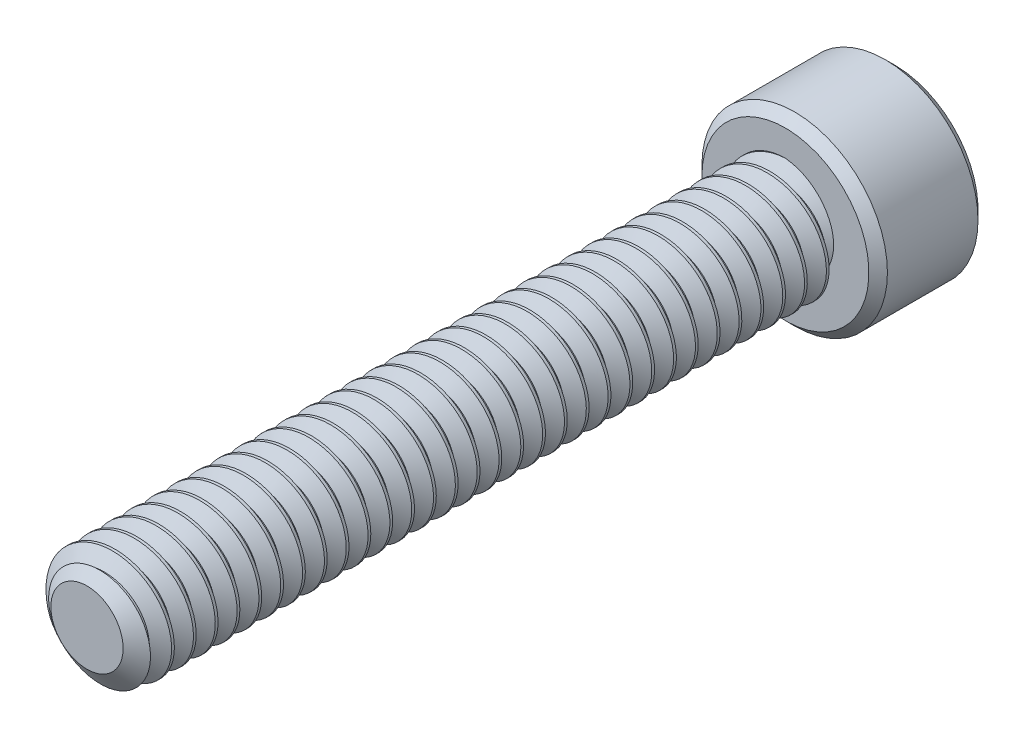
SolidWorks part; units mm, degrees
other "DetailItem1"
ref_plane "Front Plane" through (0, 0, 0) normal (0, 0, 1) x (1, 0, 0)
ref_plane "Top Plane" through (0, 0, 0) normal (0, 1, 0) x (1, 0, 0)
ref_plane "Right Plane" through (0, 0, 0) normal (1, 0, 0) x (0, 0, -1)
sketch "Sketch1" plane through (0, 0, 0) normal (0, 0, 1) x (1, 0, 0)
  circle A0 centre (0, 0) radius 2.0828
  dimension "OD" = 4.1656
extrude "Extrude1" add sketch "Sketch1" against normal blind 25.4
sketch "Sketch2" plane through (0, 0, 0) normal (0, 0, 1) x (1, 0, 0)
  circle A0 centre (0, 0) radius 2.0828 construction
  circle A1 centre (0, 0) radius 2.0828
curve "Helix/Spiral1" pitch 0.7937 height 26.1937 turns 33 parameters "pitch"=0.7937
sketch "Sketch3" plane through (0, 0, 0) normal (1, 0, 0) x (0, 0, -1)
  line L0 (-0.6945, 2.0828) -> (-0.3969, 1.5672)
  line L1 (-0.3969, 1.5672) -> (-0.2977, 1.5672)
  line L2 (-0.2977, 1.5672) -> (0, 2.0828)
  line L3 (-0.6945, 2.0828) -> (0, 2.0828)
  line L4 (-0.3473, 2.0828) -> (-0.3473, 1.5672) construction
  line L5 (-0.5457, 1.825) -> (-0.1488, 1.825) construction
  line L6 (0, 2.0828) -> (0, -2.0828) construction
  dimension "D1" = 0.0992
  dimension "D2" = 0.3969
  dimension "D3" = 60
sweep "Cut-Sweep1" cut profiles "Sketch3" path "Helix/Spiral1"
sketch "Sketch4" plane through (0, 0, 0) normal (1, 0, 0) x (0, 0, -1)
  line L0 (0.5388, 2.0828) -> (0, 1.3132)
  line L1 (0, 1.3132) -> (0, 2.0828)
  line L2 (0.5388, 2.0828) -> (0, 2.0828)
  line L3 (-0.6945, 2.0828) -> (0, 2.0828) construction
  line L4 (0, 0) -> (7.0209, 0) construction
  dimension "D1" = 55
  dimension "D2" = 0.254
revolve "Cut-Revolve1" cut sketch "Sketch4" angle 360 about L4
sketch "Sketch6" plane through (0, 0, -25.4) normal (0, 0, -1) x (-1, 0, 0)
  circle A0 centre (0, 0) radius 3.3734
  dimension "head dia" = 6.7469
extrude "Extrude2" add sketch "Sketch6" along normal blind 3.9688
sketch "Sketch7" plane through (0, 0, -29.3687) normal (0, 0, -1) x (-1, 0, 0)
  line L1 (0, 2.0622) -> (-1.7859, 1.0311)
  line L2 (-1.7859, 1.0311) -> (-1.7859, -1.0311)
  line L3 (-1.7859, -1.0311) -> (0, -2.0622)
  line L4 (0, -2.0622) -> (1.7859, -1.0311)
  line L5 (1.7859, -1.0311) -> (1.7859, 1.0311)
  line L6 (1.7859, 1.0311) -> (0, 2.0622)
  circle A0 centre (0, 0) radius 1.7859 construction
  dimension "hex dia" = 3.5719
extrude "Cut-Extrude1" cut sketch "Sketch7" against normal blind 2.6789
sketch "Sketch8" plane through (0, 0, -29.3687) normal (0, 0, -1) x (-1, 0, 0)
  circle A0 centre (0, 0) radius 2.0622
extrude "Cut-Extrude2" cut sketch "Sketch8" against normal through all draft 45
chamfer "Chamfer1" distance 0.3373 angle 45 2 edges at (-3.3734, 0, -29.3687) (-3.3734, 0, -25.4)
sketch "Sketch10" plane through (0, 0, -25.4) normal (0, 0, 1) x (1, 0, 0)
  circle A1 centre (0, 0) radius 2.0828
  circle A2 centre (0, 0) radius 2.0828
  dimension "D1" = 0
ref_plane "Plane1" through (0, 0, -22.225) normal (0, 0, 1) x (1, 0, 0)
extrude "partial thread" [suppressed] add sketch "Sketch10" along normal up to surface (15.875 mm away) separate body
chamfer "Chamfer2" [suppressed] distance 0.0833 angle 45
combine bodies "Combine1" [suppressed] operation type add bodies to combine 107 108
sketch "Sketch9" plane through (0, 0, 0) normal (1, 0, 0) x (0, 0, -1)
  line L0 (0, 2.0828) -> (0, -2.0828) construction
  line L1 (1.9844, 2.0828) -> (1.9844, -2.0828) construction
  dimension "D1" = 1.9844
equation "\"D3@Helix/Spiral1\" = \"screw length@Extrude1\"+\"pitch@Helix/Spiral1\""
equation "\"D1@Sketch3\" = \"pitch@Helix/Spiral1\"*.125"
equation "\"D2@Sketch3\" = \"pitch@Helix/Spiral1\"*.5"
equation "\"D1@Cut-Extrude1\" = \"hex dia@Sketch7\"*.75"
equation "\"D1@Chamfer1\" = \"head dia@Sketch6\"*.05"
equation "\"D1@Sketch9\" = \"pitch@Helix/Spiral1\"*2.5"
equation "\"D1@Chamfer2\"=\"OD@Sketch1\"*.02"
